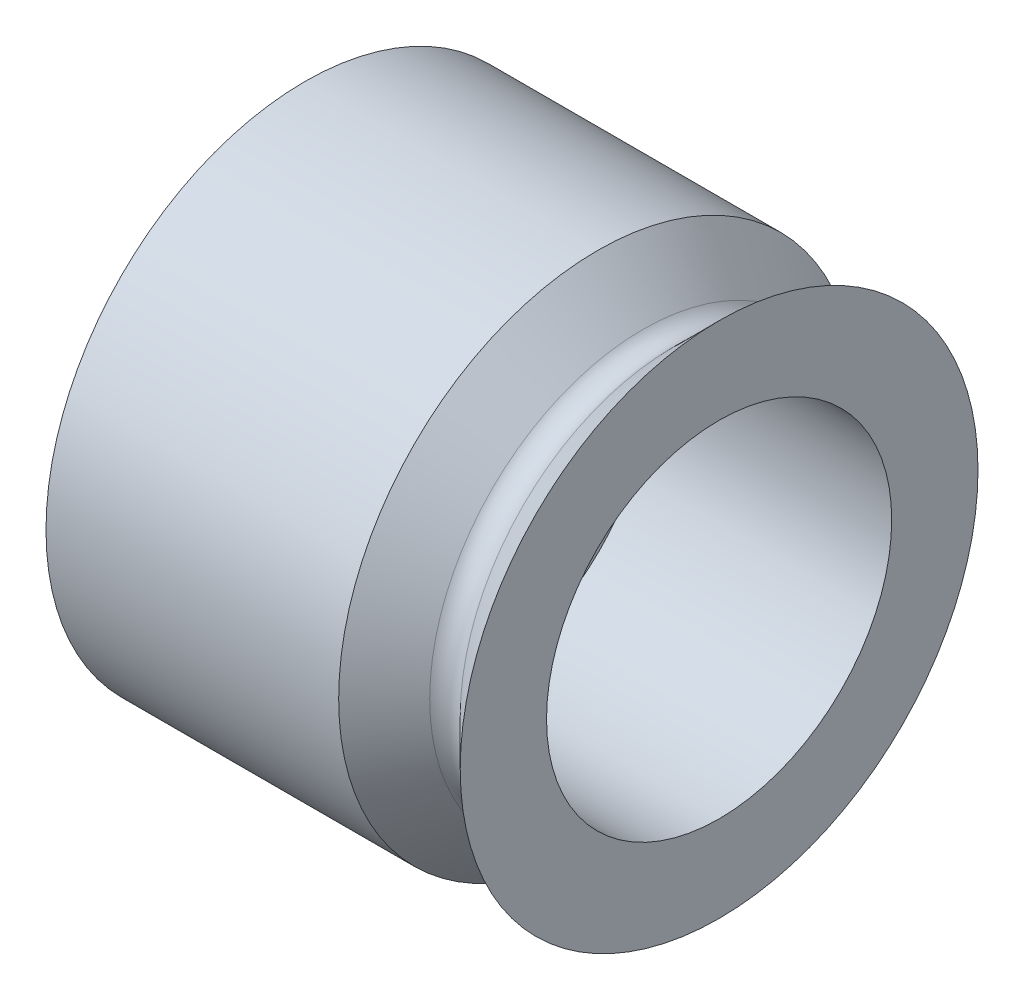
SolidWorks part; units mm, degrees
ref_plane "Front Plane" through (0, 0, 0) normal (0, 0, 1) x (1, 0, 0)
ref_plane "Top Plane" through (0, 0, 0) normal (0, 1, 0) x (1, 0, 0)
ref_plane "Right Plane" through (0, 0, 0) normal (1, 0, 0) x (0, 0, -1)
sketch "Sketch1" plane through (0, 0, 0) normal (0, 1, 0) x (1, 0, 0)
  line L0 (0, 2.6) -> (6.35, 2.6)
  line L1 (6.35, 2.6) -> (6.35, 6.35)
  line L2 (6.35, 6.35) -> (15.24, 6.35)
  line L3 (15.24, 6.35) -> (15.24, 9.525)
  line L4 (10.7675, 9.525) -> (12.4425, 7.85)
  line L5 (13.565, 7.85) -> (15.24, 9.525)
  line L6 (0, 0) -> (26.0731, 0) construction
  line L7 (10.7675, 9.525) -> (0, 9.525)
  line L8 (0, 9.525) -> (0, 2.6)
  arc A0 (12.4425, 7.85) -> (13.565, 7.85) centre (13.0037, 8.4113) ccw
  dimension "D1" = 2.6
  dimension "D6" = 45
  dimension "D7" = 0.7937
  dimension "D2" = 15.24
  dimension "D3" = 9.525
  dimension "D4" = 6.35
  dimension "D5" = 6.35
  dimension "D8" = 1.5
revolve "Revolve1" add sketch "Sketch1" angle 360 about L6
